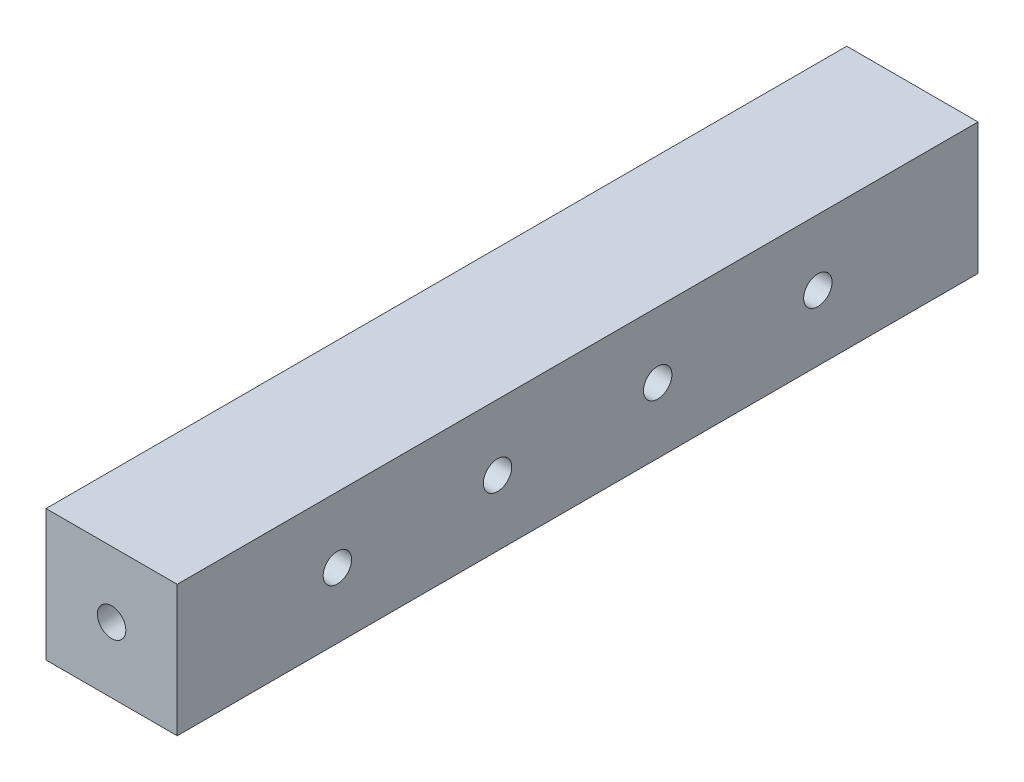
SolidWorks part; units mm, degrees
ref_plane "Front Plane" through (0, 0, 0) normal (0, 0, 1) x (1, 0, 0)
ref_plane "Top Plane" through (0, 0, 0) normal (0, 1, 0) x (1, 0, 0)
ref_plane "Right Plane" through (0, 0, 0) normal (1, 0, 0) x (0, 0, -1)
sketch "Sketch1" plane through (0, 0, 0) normal (0, 0, 1) x (1, 0, 0)
  line L1 (-12.7, -12.7) -> (12.7, -12.7)
  line L2 (-12.7, -12.7) -> (-12.7, 12.7)
  line L3 (-12.7, 12.7) -> (12.7, 12.7)
  line L4 (12.7, -12.7) -> (12.7, 12.7)
  line L5 (-12.7, -12.7) -> (12.7, 12.7) construction
  line L6 (-12.7, 12.7) -> (12.7, -12.7) construction
  point P0 (0, 0)
  dimension "D1" = 25.4
extrude "Boss-Extrude1" add sketch "Sketch1" along normal mid plane 155
sketch "Sketch2" plane through (0, 0, 77.5) normal (0, 0, 1) x (1, 0, 0)
  point P0 (0, 0)
sketch "Sketch4" plane through (12.7, 0, 0) normal (1, 0, 0) x (0, 0, -1)
  line L0 (-77.5, -12.7) -> (-77.5, 12.7) construction
  point P0 (-46.5, 0)
  point P1 (-15.5, 0)
  point P2 (15.5, 0)
  point P3 (46.5, 0)
  point P8 (0, 0)
  point P9 (0, 0)
  point P12 (0, 0)
  dimension "D1" = 31
  dimension "D2" = 31
  dimension "D3" = 31
  dimension "D4" = 31
sketch "Sketch5" plane through (0, -12.7, 0) normal (0, -1, 0) x (1, 0, 0)
  line L0 (-12.7, 77.5) -> (12.7, 77.5) construction
  line L1 (-12.7, -77.5) -> (12.7, -77.5) construction
  point P0 (0, 62)
  point P1 (0, 0)
  point P2 (0, -62)
  point P8 (0, 0)
  point P9 (0, 0)
  dimension "D1" = 15.5
  dimension "D2" = 15.5
hole_wizard "M5 Clearance Hole1" positions "Sketch6" profile "Sketch8" hole size "M5" standard "ANSI Metric"
sketch "Sketch6" plane through (12.7, 0, 0) normal (1, 0, 0) x (0, 0, -1)
  point P0 (-46.5, 0)
  point P3 (-15.5, 0)
  point P6 (15.5, 0)
  point P9 (46.5, 0)
sketch "Sketch8" plane through (12.7, 0, 46.5) normal (0, 1, 0) x (0, 0, -1)
  line L0 (0, 0) -> (0, 6.8474)
  line L1 (0, 6.8474) -> (2.75, 5.195)
  line L2 (2.75, 5.195) -> (2.75, 0)
  line L5 (2.75, 0) -> (0, 0)
  line L10 (0, 6.8474) -> (-2.75, 5.195) construction
  line L11 (0, -6.35) -> (0, 107.95) construction
  dimension "Hole Dia." = 5.5
  dimension "Hole Depth" = 5.195
  dimension "Drill Angle" = 118
hole_wizard "M5 Clearance Hole2" positions "Sketch9" profile "Sketch10" hole size "M5" standard "ANSI Metric"
sketch "Sketch9" plane through (0, -12.7, 0) normal (0, -1, 0) x (-1, 0, 0)
  point P0 (0, -62)
  point P3 (0, 0)
  point P6 (0, 62)
sketch "Sketch10" plane through (0, -12.7, 62) normal (1, 0, 0) x (0, 0, -1)
  line L0 (0, 0) -> (0, 6.8524)
  line L1 (0, 6.8524) -> (2.75, 5.2)
  line L2 (2.75, 5.2) -> (2.75, 0)
  line L5 (2.75, 0) -> (0, 0)
  line L10 (0, 6.8524) -> (-2.75, 5.2) construction
  line L11 (0, -6.35) -> (0, 107.95) construction
  dimension "Hole Dia." = 5.5
  dimension "Hole Depth" = 5.2
  dimension "Drill Angle" = 118
hole_wizard "M5 Clearance Hole3" positions "Sketch11" profile "Sketch12" hole size "M5" standard "ANSI Metric"
sketch "Sketch11" plane through (0, 0, 77.5) normal (0, 0, 1) x (1, 0, 0)
  point P0 (0, 0)
sketch "Sketch12" plane through (0, 0, 77.5) normal (1, 0, 0) x (0, -1, 0)
  line L0 (0, 0) -> (0, 6.1524)
  line L1 (0, 6.1524) -> (2.75, 4.5)
  line L2 (2.75, 4.5) -> (2.75, 0)
  line L5 (2.75, 0) -> (0, 0)
  line L10 (0, 6.1524) -> (-2.75, 4.5) construction
  line L11 (0, -6.35) -> (0, 107.95) construction
  dimension "Hole Dia." = 5.5
  dimension "Hole Depth" = 4.5
  dimension "Drill Angle" = 118
